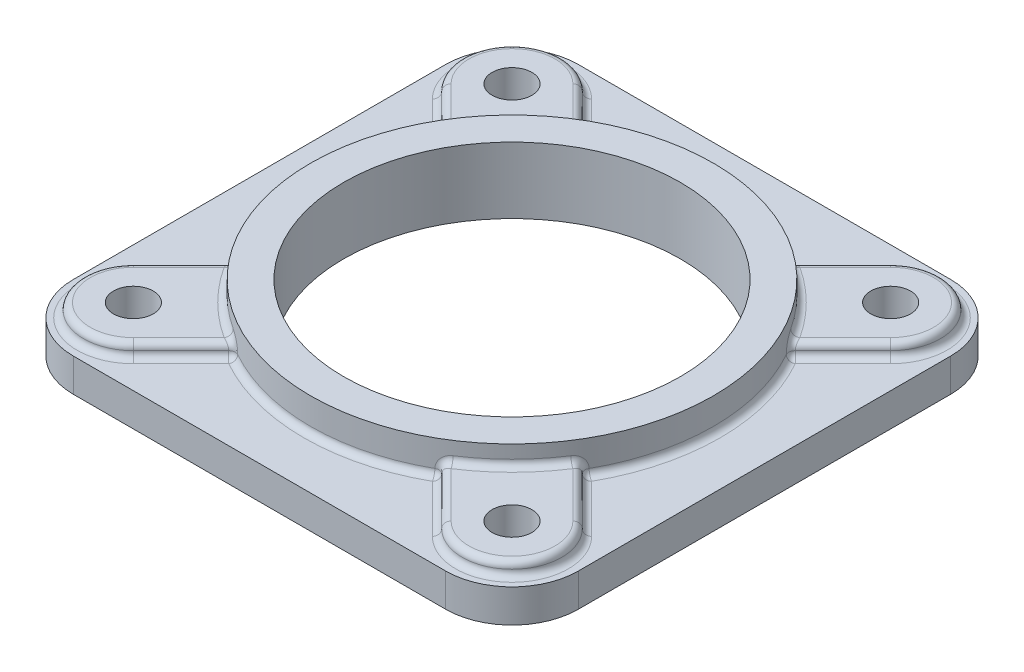
SolidWorks part; units mm, degrees
ref_plane "Front Plane" through (0, 0, 0) normal (0, 0, 1) x (1, 0, 0)
ref_plane "Top Plane" through (0, 0, 0) normal (0, 1, 0) x (1, 0, 0)
ref_plane "Right Plane" through (0, 0, 0) normal (1, 0, 0) x (0, 0, -1)
sketch "Sketch1" plane through (0, 0, 0) normal (0, 1, 0) x (1, 0, 0)
  line L1 (38.1, -38.1) -> (-38.1, -38.1)
  line L2 (38.1, -38.1) -> (38.1, 38.1)
  line L3 (38.1, 38.1) -> (-38.1, 38.1)
  line L4 (-38.1, -38.1) -> (-38.1, 38.1)
  line L5 (38.1, -38.1) -> (-38.1, 38.1) construction
  line L6 (38.1, 38.1) -> (-38.1, -38.1) construction
  circle A0 centre (0, 0) radius 25.4
  circle A1 centre (0, 0) radius 35.4 construction
  dimension "D1" = 50.8
  dimension "D2" = 10
  dimension "D3" = 76.2
extrude "Boss-Extrude1" add sketch "Sketch1" along normal blind 5
sketch "Sketch2" plane through (0, 5, 0) normal (0, 1, 0) x (1, 0, 0)
  circle A0 centre (0, 0) radius 25.4
  circle A1 centre (0, 0) radius 30.4
  circle A2 centre (0, 0) radius 25.4 construction
  dimension "D1" = 5
extrude "Boss-Extrude2" add sketch "Sketch2" along normal blind 5
fillet "Fillet2" radius 10 4 edges at (-38.1, 2.5, -38.1) (38.1, 2.5, -38.1) (38.1, 2.5, 38.1) (-38.1, 2.5, 38.1)
sketch "Sketch5" plane through (0, 5, 0) normal (0, 1, 0) x (1, 0, 0)
  line L0 (-26.1349, 15.5283) -> (-33.8704, 23.2638)
  line L1 (38.1, -38.1) -> (-38.1, -38.1) construction
  line L2 (38.1, -38.1) -> (38.1, 38.1) construction
  line L3 (38.1, 38.1) -> (-38.1, 38.1) construction
  line L4 (-38.1, -38.1) -> (-38.1, 38.1) construction
  line L5 (38.1, -38.1) -> (-38.1, 38.1) construction
  line L6 (38.1, 38.1) -> (-38.1, -38.1) construction
  line L7 (-23.2638, 33.8704) -> (-15.5283, 26.1349)
  line L8 (-38.1, 28.1) -> (-38.1, -28.1) construction
  circle A0 centre (0, 0) radius 40.4 construction
  circle A1 centre (0, 0) radius 30.4 construction
  arc A2 (-33.8704, 23.2638) -> (-23.2638, 33.8704) centre (-28.5671, 28.5671) cw
  arc A3 (-26.1349, 15.5283) -> (-15.5283, 26.1349) centre (0, 0) cw
  point P0 (0, 0)
  point P16 (0, 0)
  point P17 (-40.179, 40.179)
  dimension "D1" = 80.8
  dimension "D2" = 7.5
  dimension "D3" = 7.5
extrude "Boss-Extrude3" add sketch "Sketch5" along normal blind 2
pattern_circular "CirPattern1" count 4 over 360 about axis through (0, 0, 0) along (0, 1, 0) of "Boss-Extrude3"
sketch "Sketch3" plane through (0, 7, 0) normal (0, 1, 0) x (1, 0, 0)
  line L1 (28.5671, -28.5671) -> (-28.5671, -28.5671) construction
  line L2 (28.5671, -28.5671) -> (28.5671, 28.5671) construction
  line L3 (28.5671, 28.5671) -> (-28.5671, 28.5671) construction
  line L4 (-28.5671, -28.5671) -> (-28.5671, 28.5671) construction
  line L5 (28.5671, -28.5671) -> (-28.5671, 28.5671) construction
  line L6 (28.5671, 28.5671) -> (-28.5671, -28.5671) construction
  circle A0 centre (0, 0) radius 40.4 construction
  circle A1 centre (0, 0) radius 25.4 construction
  point P0 (-28.5671, -28.5671)
  point P3 (28.5671, -28.5671)
  point P5 (28.5671, 28.5671)
  point P7 (-28.5671, 28.5671)
  dimension "D1" = 15
hole_wizard "Ø6.0mm Dowel Hole1" positions "Sketch3" profile "Sketch4" hole size "Ø6.0" standard "ANSI Metric" end condition through all
sketch "Sketch4" plane through (-28.5671, 7, 28.5671) normal (1, 0, 0) x (0, 0, 1)
  line L0 (0, 0) -> (0, 7)
  line L1 (0, 7) -> (3, 7)
  line L2 (3, 7) -> (3, 0)
  line L5 (3, 0) -> (0, 0)
  line L11 (0, -6.35) -> (0, 107.95) construction
  dimension "Thru Hole Dia." = 6
  dimension "Thru Hole Depth" = 7
fillet "Fillet1" radius 1 32 edges at (-19.396, 7, 30.0027) (-33.8704, 7, 33.8704) (30.0027, 7, 19.396) (33.8704, 7, 33.8704) (19.396, 7, -30.0027) (33.8704, 7, -33.8704) (19.396, 5, -30.0027) (33.8704, 5, -33.8704) (30.0027, 5, 19.396) (33.8704, 5, 33.8704) (-19.396, 5, -30.0027) (-33.8704, 5, -33.8704) (-30.0027, 5, 19.396) (-33.8704, 5, 33.8704) (30.4, 5, 0) (21.496, 7, 21.496) (0, 5, 30.4) (-21.496, 7, 21.496) (-30.4, 5, 0) (-21.496, 7, -21.496) (0, 5, -30.4) (21.496, 7, -21.496) (-30.0027, 7, 19.396) (19.396, 7, 30.0027) (30.0027, 7, -19.396) (30.0027, 5, -19.396) (19.396, 5, 30.0027) (-30.0027, 5, -19.396) (-19.396, 5, 30.0027) (-19.396, 7, -30.0027) (-33.8704, 7, -33.8704) (-30.0027, 7, -19.396)
equation "\"D2@Sketch5\"=\"D3@Sketch5\""
